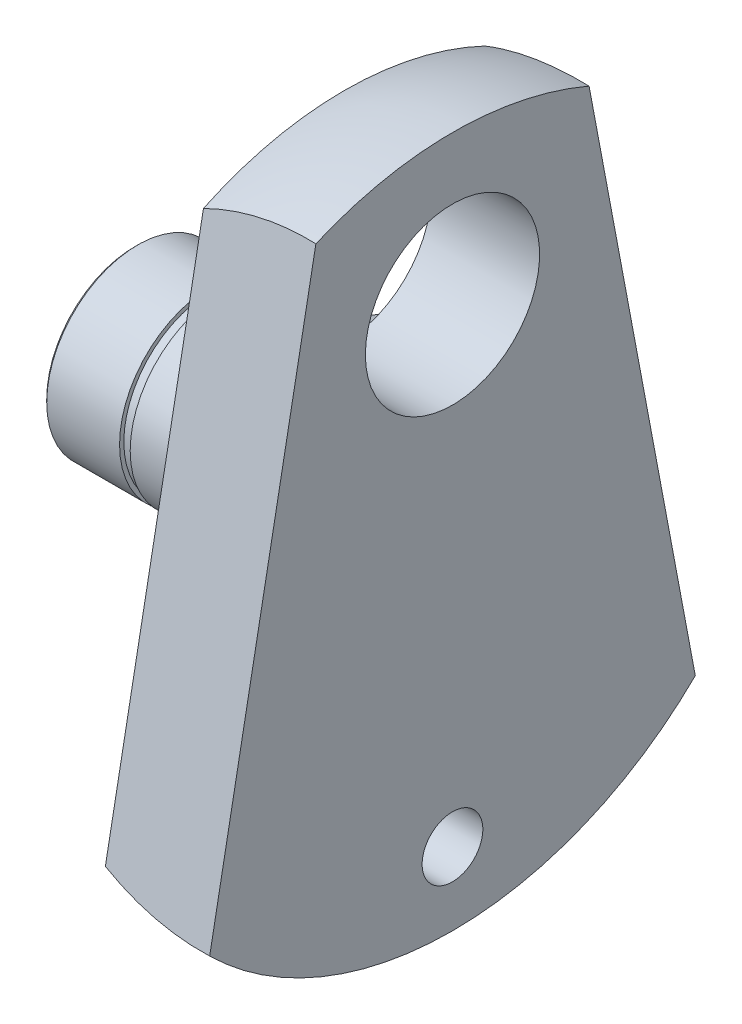
SolidWorks part; units mm, degrees
ref_plane "Front Plane" through (0, 0, 0) normal (0, 0, 1) x (1, 0, 0)
ref_plane "Top Plane" through (0, 0, 0) normal (0, 1, 0) x (1, 0, 0)
ref_plane "Right Plane" through (0, 0, 0) normal (1, 0, 0) x (0, 0, -1)
sketch "Sketch1" plane through (0, 0, 0) normal (0, 0, 1) x (1, 0, 0)
  line L0 (0, 0) -> (52.34, 0) construction
  line L1 (52.34, 56.95) -> (52.34, 0)
  line L2 (0, 14.5) -> (0.5, 15)
  line L3 (0, 12.5) -> (0.5, 12)
  line L4 (34.49, 19) -> (34.49, 54)
  line L5 (0, 14.5) -> (0, 12.5)
  line L6 (52.34, 0) -> (5.1, 0)
  line L7 (34.49, 19) -> (32.68, 19)
  line L10 (0.5, 15) -> (12.5, 15)
  line L11 (32.68, 15) -> (32.68, 19)
  line L14 (12.5, 15) -> (12.5, 14.3)
  line L15 (12.5, 14.3) -> (14.25, 14.3)
  line L16 (14.25, 14.3) -> (14.25, 15)
  line L17 (14.25, 15) -> (32.68, 15)
  line L19 (0.5, 12) -> (5.1, 12)
  line L20 (5.1, 12) -> (5.1, 0)
  arc A0 (34.49, 54) -> (52.34, 56.95) centre (50.9917, 9.6296) cw
  point P18 (0, 15)
  point P28 (0, 12)
revolve "Revolve1" add sketch "Sketch1" angle 360 about L0
sketch "Sketch2" plane through (34.49, 0, 0) normal (-1, 0, 0) x (0, 0, 1)
  line L8 (-22.5, 52.3168) -> (-40, -40.5646)
  line L9 (22.5, 52.3378) -> (40, -40.5646)
  circle A2 centre (0, 0) radius 56.9692 construction
  circle A3 centre (0, 0) radius 56.95 construction
  arc A4 (-40, -40.5646) -> (40, -40.5646) centre (0, 0) ccw
  arc A5 (22.5, 52.3378) -> (-22.5, 52.3378) centre (0, 0) ccw
extrude "Cut-Extrude3" cut sketch "Sketch2" against normal through all and the other way through all flip side to cut
sketch "Sketch3" plane through (34.49, 0, 0) normal (-1, 0, 0) x (0, 0, 1)
  circle A0 centre (0, 32.4) radius 14.35
  circle A1 centre (0.0044, -44.95) radius 5
extrude "Cut-Extrude4" cut sketch "Sketch3" against normal mid plane 50
sketch "Sketch4" plane through (5.1, 0, 0) normal (-1, 0, 0) x (0, 0, 1)
  circle A0 centre (0, 0) radius 4.7
  circle A3 centre (0, 9) radius 2
extrude "Cut-Extrude5" cut sketch "Sketch4" against normal blind 6
sketch "Sketch5" plane through (5.1, 0, 0) normal (-1, 0, 0) x (0, 0, 1)
  circle A0 centre (0, 0) radius 3.35
extrude "Cut-Extrude6" cut sketch "Sketch5" against normal blind 35.7
